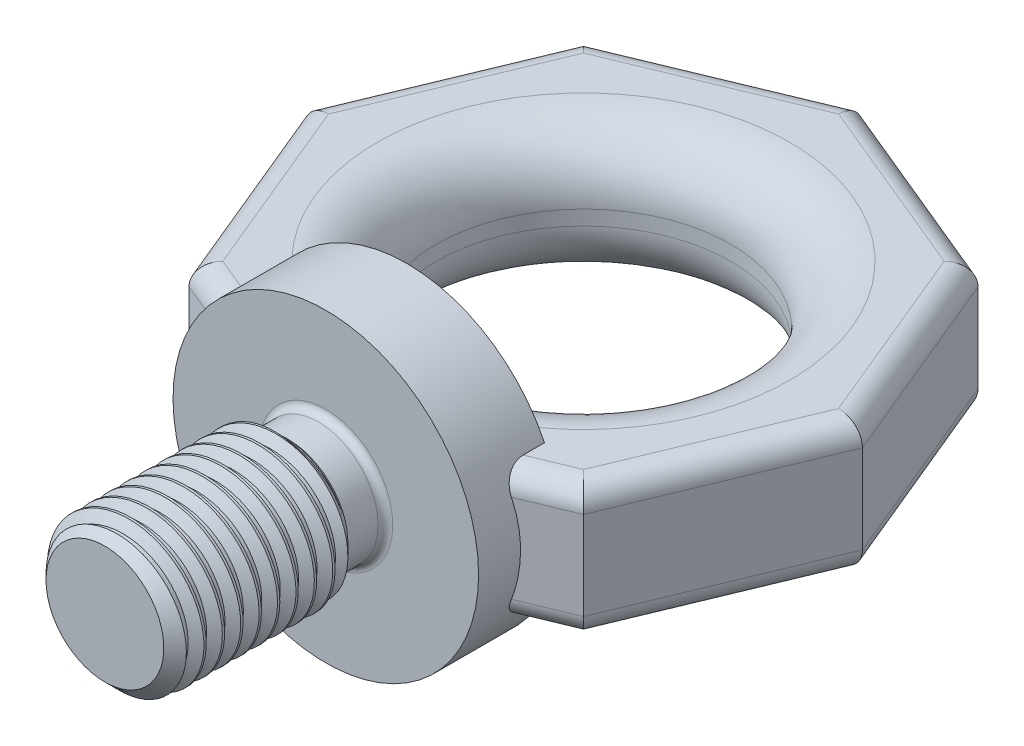
SolidWorks part; units mm, degrees
material "1.0553 (S355J0)"
ref_plane "XY Plane" through (0, 0, 0) normal (0, 0, 1) x (1, 0, 0)
ref_plane "XZ Plane" through (0, 0, 0) normal (0, 1, 0) x (1, 0, 0)
ref_plane "YZ Plane" through (0, 0, 0) normal (1, 0, 0) x (0, 0, -1)
sketch "Sketch1" plane through (0, 0, 0) normal (0, 1, 0) x (1, 0, 0)
  line L0 (0, 0) -> (0, 37.8837) construction
  line L7 (0, 37.8837) -> (-26.7878, 26.7878)
  line L8 (-26.7878, 26.7878) -> (-37.8837, 0)
  line L9 (-37.8837, 0) -> (-26.7878, -26.7878)
  line L10 (-26.7878, -26.7878) -> (0, -37.8837)
  line L11 (0, -37.8837) -> (26.7878, -26.7878)
  line L12 (26.7878, -26.7878) -> (37.8837, 0)
  line L13 (37.8837, 0) -> (26.7878, 26.7878)
  line L14 (26.7878, 26.7878) -> (0, 37.8837)
  circle A1 centre (0, 0) radius 35 construction
  dimension "D1" = 70
extrude "Boss-Extrude1" add sketch "Sketch1" along normal mid plane 18
sketch "Sketch2" plane through (0, 9, 0) normal (0, 1, 0) x (1, 0, 0)
  circle A0 centre (0, 0) radius 20
  dimension "D1" = 40
extrude "Cut-Extrude1" cut sketch "Sketch2" against normal up to next
fillet "Fillet1" radius 8 2 edges at (0, -9, 20) (0, 9, 20)
fillet "Fillet2" radius 3 8 edges at (-32.3358, 9, 13.3939) (-13.3939, 9, 32.3358) (13.3939, 9, 32.3358) (32.3358, 9, 13.3939) (32.3358, 9, -13.3939) (13.3939, 9, -32.3358) (-13.3939, 9, -32.3358) (-32.3358, 9, -13.3939)
fillet "Fillet3" radius 3 8 edges at (32.3358, -9, 13.3939) (13.3939, -9, 32.3358) (-13.3939, -9, 32.3358) (-32.3358, -9, 13.3939) (-32.3358, -9, -13.3939) (-13.3939, -9, -32.3358) (13.3939, -9, -32.3358) (32.3358, -9, -13.3939)
ref_plane "Plane1" through (0, 0, 24) normal (0, 0, 1) x (1, 0, 0)
sketch "Sketch3" plane through (0, 0, 24) normal (0, 0, 1) x (1, 0, 0)
  line L0 (0, 6) -> (0, -6) construction
  circle A0 centre (0, 0) radius 20.75
  dimension "D1" = 41.5
extrude "Boss-Extrude2" add sketch "Sketch3" along normal offset from surface (41 mm away) 65 contours A0 up to plane "XY Plane"
sketch "Sketch5" plane through (0, 0, 0) normal (0, 1, 0) x (1, 0, 0)
  line L0 (8, -65) -> (10, -63)
  line L1 (-20.75, -65) -> (20.75, -65) construction
  line L2 (10, -63) -> (10, -42)
  line L3 (10, -42) -> (8.1, -40.1)
  line L4 (8.1, -40.1) -> (8.1, -36)
  line L5 (9.1, -35) -> (30, -35)
  line L6 (30, -35) -> (30, -70)
  line L7 (30, -70) -> (8, -70)
  line L8 (8, -70) -> (8, -65)
  line L9 (0, 0) -> (0, -82.5386) construction
  arc A0 (8.1, -36) -> (9.1, -35) centre (9.1, -36) cw
  point P13 (8.1, -37.991)
  point P14 (0, 0)
  dimension "D10" = 1
  dimension "D1" = 20
  dimension "D2" = 16.2
  dimension "D3" = 60
  dimension "D4" = 30
  dimension "D5" = 7
  dimension "D6" = 45
  dimension "D7" = 45
  dimension "D8" = 2
  dimension "D9" = 5
revolve "Cut-Revolve1" cut sketch "Sketch5" angle 360 about L9
thread "Thread1" pitch 2.5 method cut trim with start face yes profile "Thread Profile1" start angle 0, offset 2.5, length 0, pitch 2.5, diameter 20
ref_plane "Plane2" through (-10, 0, 67.5) normal (0, -1, 0) x (-1, 0, 0)
sketch "Thread Profile1" plane through (-10, 0, 67.5) normal (0, -1, 0) x (-1, 0, 0)
  line L0 (0, 0) -> (0, 2.5) construction
  line L11 (0, 0) -> (0, 2.1875)
  line L12 (0, 2.1875) -> (-1.3532, 1.4062)
  line L13 (-1.3532, 1.4062) -> (-1.3532, 0.7812)
  line L15 (-1.3532, 0.7812) -> (0, 0)
  line L17 (-1.3532, 1.0937) -> (0, 1.0937) construction
  point P2 (0, 0)
  dimension "Pitch" = 2.5
  dimension "Profile_Angle" = 60
  dimension "Profile_Land" = 0.625
  dimension "Profile_Height" = 1.3532
